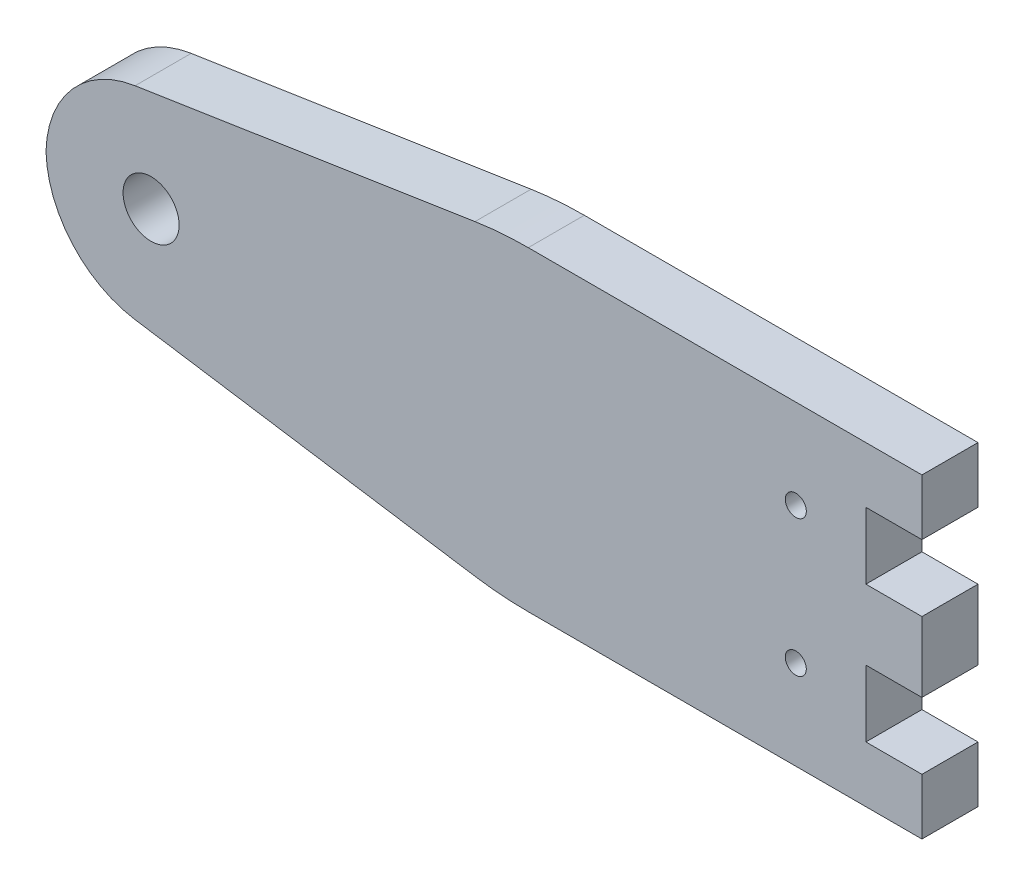
SolidWorks part; units mm, degrees
ref_plane "Front Plane" through (0, 0, 0) normal (0, 0, 1) x (1, 0, 0)
ref_plane "Top Plane" through (0, 0, 0) normal (0, 1, 0) x (1, 0, 0)
ref_plane "Right Plane" through (0, 0, 0) normal (1, 0, 0) x (0, 0, -1)
sketch "Sketch1" plane through (0, 0, 0) normal (0, 0, 1) x (1, 0, 0)
  line L0 (0, 22.5) -> (0, 27.5)
  line L1 (0, 0) -> (-125, 0)
  line L2 (0, 0) -> (0, 45)
  line L3 (0, 45) -> (-125, 45)
  line L4 (-125, 0) -> (-125, 45)
  line L5 (0, 45) -> (-8, 45)
  line L6 (0, 45) -> (0, 37)
  line L7 (0, 37) -> (-8, 37)
  line L8 (-8, 45) -> (-8, 37)
  line L9 (0, 0) -> (-8, 0)
  line L10 (0, 0) -> (0, 8)
  line L11 (0, 8) -> (-8, 8)
  line L12 (-8, 0) -> (-8, 8)
  line L13 (0, 27.5) -> (-8, 27.5)
  line L14 (-8, 27.5) -> (-8, 17.5)
  line L15 (-8, 17.5) -> (0, 17.5)
  line L16 (0, 17.5) -> (0, 22.5)
  line L17 (-125, 22.5) -> (-105, 22.5)
  line L18 (-105, 22.5) -> (-110, 22.5)
  line L19 (-110, 22.5) -> (-10, 22.5)
  line L21 (-8, 8) -> (-8, 17.5)
  line L30 (-75, 18.5) -> (-85, 18.5)
  line L31 (-75, 18.5) -> (-75, 26.5)
  line L32 (-8, 17.5) -> (-8, 37)
  line L33 (-75, 26.5) -> (-85, 26.5)
  line L34 (-85, 18.5) -> (-85, 26.5)
  line L35 (-75, 18.5) -> (-85, 26.5) construction
  line L36 (-75, 26.5) -> (-85, 18.5) construction
  dimension "D1" = 125
  dimension "D2" = 45
  dimension "D3" = 5
  dimension "D4" = 10
  dimension "D5" = 8
  dimension "D6" = 8
  dimension "D7" = 8
extrude "Boss-Extrude1" add sketch "Sketch1" along normal blind 8 contours L12 L1 L2 L11 | L14 L15 L2 L0 L13 | L3 L8 L7 L2 | L31 L4 L1 L12 L21 L14 L32 L8 L3 | L34 L30 L31 L19 | L34 L19 L31 L33 region at (-4, 22.5, 0) region at (-4, 41, 0) region at (-80, 24.5, 0) region at (-80, 20.5, 0) region at (-9.2536, 22.5, 0) region at (-4, 4, 0)
chamfer "Chamfer1" distance 10 distance2 65 1 edges at (-125, 0, 4) first distance on face at (-125, 22.5, 4)
chamfer "Chamfer2" distance 65 distance2 10 1 edges at (-125, 45, 4) first distance on face at (-62.5, 45, 4)
fillet "Fillet2" radius 15 2 edges at (-125, 10, 4) (-125, 35, 4)
fillet "Fillet3" radius 50 2 edges at (-60, 0, 4) (-60, 45, 4)
sketch "Sketch2" plane through (0, 0, 8) normal (0, 0, 1) x (1, 0, 0)
  circle A0 centre (-110, 22.8688) radius 4
extrude "Cut-Extrude1" cut sketch "Sketch2" against normal blind 80
sketch "Sketch4" plane through (0, 0, 8) normal (0, 0, 1) x (1, 0, 0)
  line L0 (0, 45) -> (-56.1763, 45) construction
  line L1 (-8, 27.5) -> (-8, 37) construction
  line L2 (-8, 8) -> (-8, 17.5) construction
  line L3 (0, 0) -> (-56.1763, 0) construction
  circle A0 centre (-18, 32.25) radius 1.5
  circle A1 centre (-18, 12.75) radius 1.5
  dimension "D1" = 3
  dimension "D2" = 12.75
  dimension "D3" = 10
  dimension "D4" = 3
  dimension "D5" = 10
  dimension "D6" = 12.75
extrude "Cut-Extrude3" cut sketch "Sketch4" against normal blind 15
